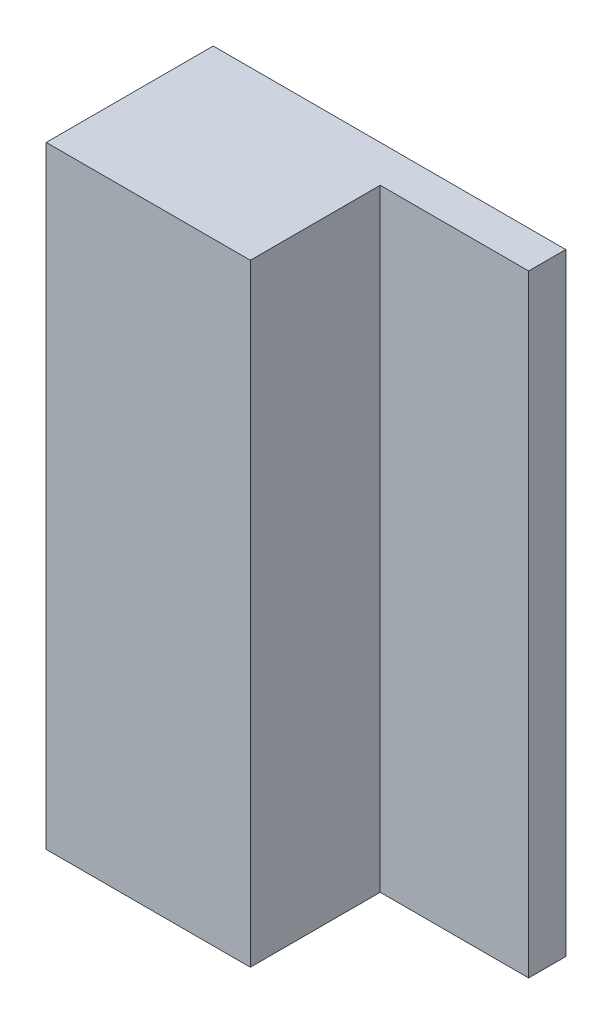
SolidWorks part; units mm, degrees
ref_plane "Front Plane" through (0, 0, 0) normal (0, 0, 1) x (1, 0, 0)
ref_plane "Top Plane" through (0, 0, 0) normal (0, 1, 0) x (1, 0, 0)
ref_plane "Right Plane" through (0, 0, 0) normal (1, 0, 0) x (0, 0, -1)
sketch "Sketch1" plane through (0, 0, 0) normal (0, 0, 1) x (1, 0, 0)
  line L1 (0, 0) -> (19, 0)
  line L2 (0, 0) -> (0, 33)
  line L3 (0, 33) -> (19, 33)
  line L4 (19, 0) -> (19, 33)
  dimension "D1" = 33
  dimension "D2" = 19
extrude "Boss-Extrude1" add sketch "Sketch1" along normal blind 9
sketch "Sketch3" plane through (0, 0, 9) normal (0, 0, 1) x (1, 0, 0)
  line L0 (0, 0) -> (19, 0) construction
  line L1 (19, 33) -> (11, 33)
  line L2 (19, 33) -> (19, 0)
  line L3 (19, 0) -> (11, 0)
  line L4 (11, 33) -> (11, 0)
  dimension "D1" = 8
extrude "Cut-Extrude1" cut sketch "Sketch3" against normal blind 7
